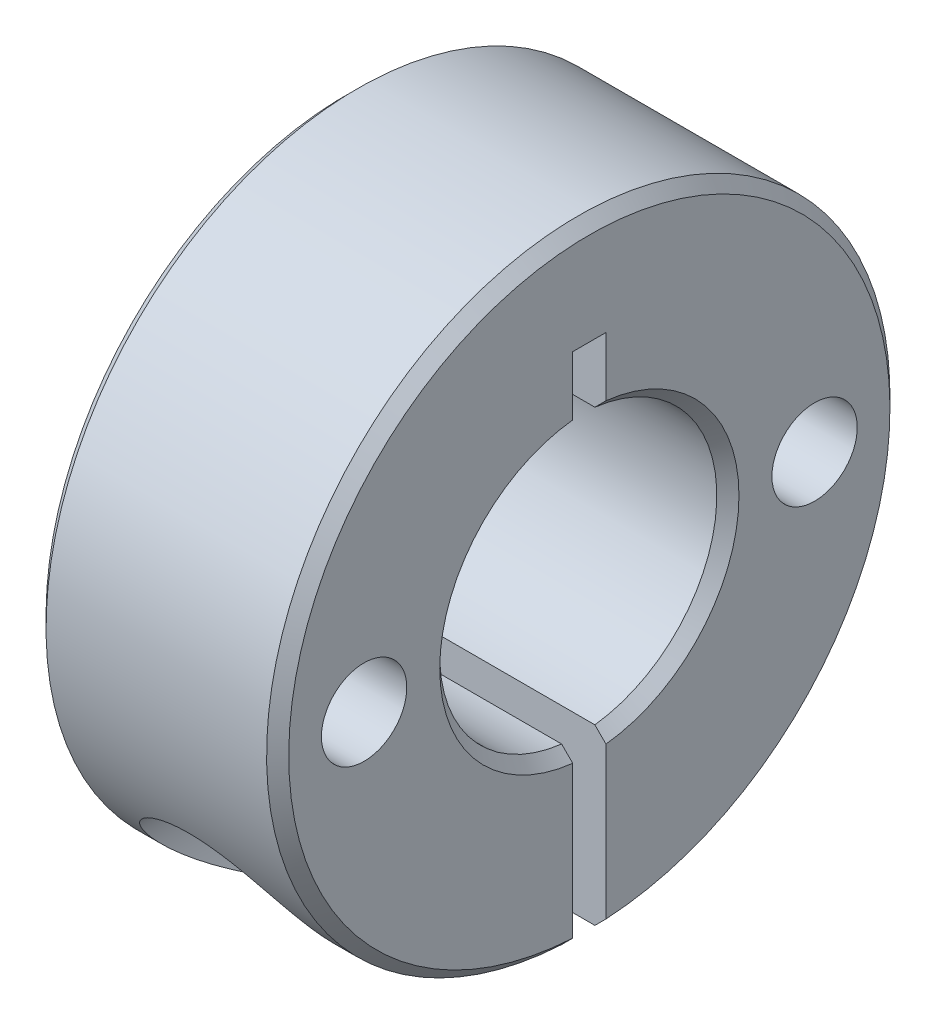
SolidWorks part; units mm, degrees
ref_plane "Front Plane" through (0, 0, 0) normal (0, 0, 1) x (1, 0, 0)
ref_plane "Top Plane" through (0, 0, 0) normal (0, 1, 0) x (1, 0, 0)
ref_plane "Right Plane" through (0, 0, 0) normal (1, 0, 0) x (0, 0, -1)
ref_plane "Plane4" through (0, 0, 0) normal (0, 0, 1) x (1, 0, 0)
sketch "Sketch1" plane through (0, 0, 0) normal (0, 0, 1) x (1, 0, 0)
  line L0 (-5.5626, 6.858) -> (-5.0546, 6.35)
  line L1 (-5.0546, 6.35) -> (5.0546, 6.35)
  line L2 (5.0546, 6.35) -> (5.5626, 6.858)
  line L3 (5.5626, 6.858) -> (5.5626, 13.7795)
  line L4 (5.5626, 13.7795) -> (5.0546, 14.2875)
  line L5 (5.0546, 14.2875) -> (-5.0546, 14.2875)
  line L6 (-5.0546, 14.2875) -> (-5.5626, 13.7795)
  line L7 (-5.5626, 13.7795) -> (-5.5626, 6.858)
  line L8 (5.5626, 0) -> (-5.5626, 0) construction
revolve "Revolve1" add sketch "Sketch1" angle 360 about L8 reverse direction yes
ref_plane "Plane5" through (0, 0, 0) normal (1, 0, 0) x (0, 0, -1)
sketch "Sketch2" plane through (0, 0, 0) normal (1, 0, 0) x (0, 0, -1)
  line L0 (-0.762, 9.525) -> (-0.762, -14.2875)
  line L1 (-0.762, -14.2875) -> (0.762, -14.2875)
  line L2 (0.762, -14.2875) -> (0.762, 9.525)
  line L3 (0.762, 9.525) -> (-0.762, 9.525)
extrude "Cut-Extrude1" cut sketch "Sketch2" against normal blind 5.5626 and the other way blind 5.5626
ref_plane "Plane6" through (0, 0, 0) normal (1, 0, 0) x (0, 0, -1)
sketch "Sketch3" plane through (0, 0, 0) normal (1, 0, 0) x (0, 0, -1)
  line L0 (-14.2875, -10.3124) -> (-14.2875, -6.35)
  line L1 (-14.2875, -6.35) -> (-3.5814, -6.35)
  line L2 (-3.5814, -6.35) -> (-3.5814, -8.0264)
  line L3 (-3.5814, -8.0264) -> (0, -8.0264)
  line L4 (0, -8.0264) -> (0, -10.3124)
  line L5 (0, -10.3124) -> (-14.2875, -10.3124)
  line L6 (0, -10.3124) -> (-14.2875, -10.3124) construction
revolve "Cut-Revolve1" cut sketch "Sketch3" angle 360 about L6 reverse direction yes
ref_plane "Plane7" through (0, 0, 0) normal (1, 0, 0) x (0, 0, -1)
sketch "Sketch4" plane through (0, 0, 0) normal (1, 0, 0) x (0, 0, -1)
  line L0 (0.762, -10.3124) -> (0.762, -8.2296)
  line L1 (0.762, -8.2296) -> (1.1938, -8.6614)
  line L2 (1.1938, -8.6614) -> (16.2306, -8.6614)
  line L3 (16.2306, -8.6614) -> (16.2306, -10.3124)
  line L4 (16.2306, -10.3124) -> (0.762, -10.3124)
  line L5 (16.2306, -10.3124) -> (0.762, -10.3124) construction
revolve "Cut-Revolve2" cut sketch "Sketch4" angle 360 about L5 reverse direction yes
ref_plane "Plane8" through (0, 0, 0) normal (0, 1, 0) x (1, 0, 0)
sketch "Sketch5" plane through (0, 0, 0) normal (0, 1, 0) x (1, 0, 0)
  line L0 (-5.5626, 10.3251) -> (-5.5626, 12.2809)
  line L1 (-5.5626, 12.2809) -> (5.5626, 12.2809)
  line L2 (5.5626, 12.2809) -> (5.5626, 10.3251)
  line L3 (5.5626, 10.3251) -> (-5.5626, 10.3251)
  line L4 (5.5626, 10.3251) -> (-5.5626, 10.3251) construction
revolve "Cut-Revolve3" cut sketch "Sketch5" angle 360 about L4 reverse direction yes
ref_plane "Plane9" through (0, 0, 0) normal (0, 1, 0) x (1, 0, 0)
sketch "Sketch6" plane through (0, 0, 0) normal (0, 1, 0) x (1, 0, 0)
  line L0 (-5.5626, -10.3251) -> (-5.5626, -8.3693)
  line L1 (-5.5626, -8.3693) -> (5.5626, -8.3693)
  line L2 (5.5626, -8.3693) -> (5.5626, -10.3251)
  line L3 (5.5626, -10.3251) -> (-5.5626, -10.3251)
  line L4 (5.5626, -10.3251) -> (-5.5626, -10.3251) construction
revolve "Cut-Revolve4" cut sketch "Sketch6" angle 360 about L4 reverse direction yes
